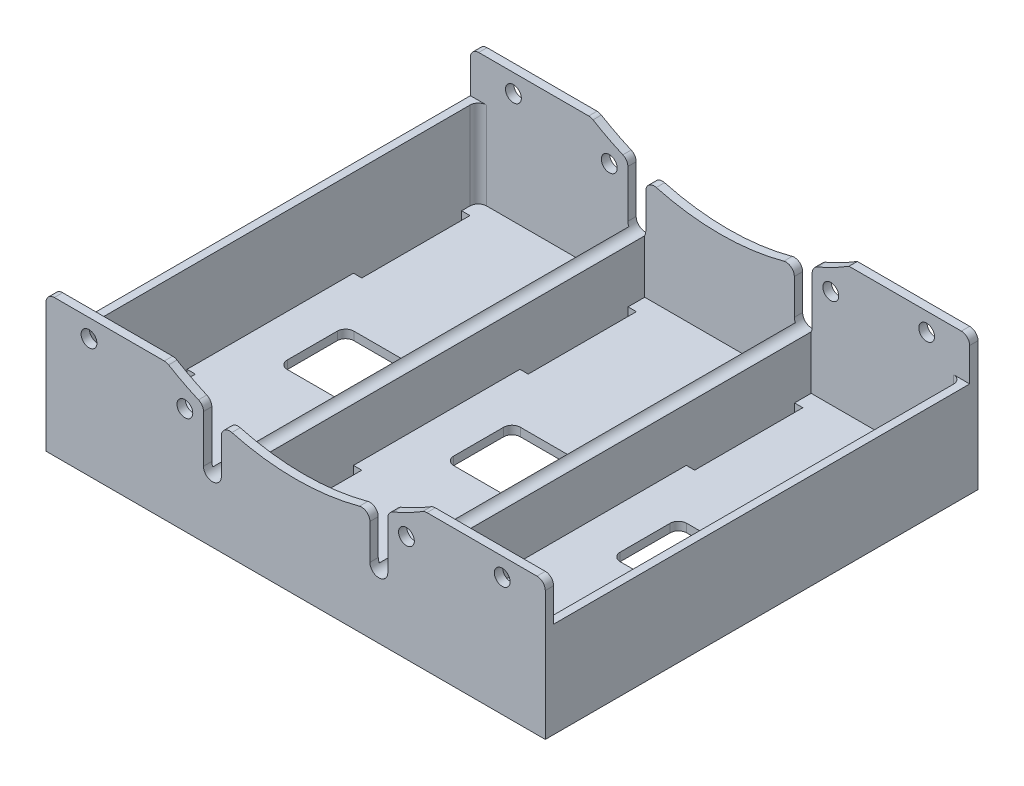
SolidWorks part; units mm, degrees
ref_plane "Front Plane" through (0, 0, 0) normal (0, 0, 1) x (1, 0, 0)
ref_plane "Top Plane" through (0, 0, 0) normal (0, 1, 0) x (1, 0, 0)
ref_plane "Right Plane" through (0, 0, 0) normal (1, 0, 0) x (0, 0, -1)
sketch "Sketch1" plane through (0, 0, 0) normal (0, 1, 0) x (1, 0, 0)
  line L1 (-60, -52) -> (60, -52)
  line L2 (-60, -52) -> (-60, 52)
  line L3 (-60, 52) -> (60, 52)
  line L4 (60, -52) -> (60, 52)
  line L5 (-60, -52) -> (60, 52) construction
  line L6 (-60, 52) -> (60, -52) construction
  point P0 (0, 0)
  dimension "D1" = 120
  dimension "D2" = 104
extrude "Boss-Extrude1" add sketch "Sketch1" along normal blind 2
sketch "Sketch3" plane through (0, 2, 0) normal (0, 1, 0) x (1, 0, 0)
  line L0 (20, 52) -> (20, 68.7594) construction
  line L1 (20, 68.7594) -> (-20, 68.7594) construction
  line L2 (60, 52) -> (-60, 52) construction
  line L3 (-21.8986, 52) -> (-18.1014, 52) construction
  line L4 (-21.8986, 52) -> (-21.8986, -52) construction
  line L5 (-60, -52) -> (60, -52) construction
  line L6 (-20, 68.7594) -> (-20, 52) construction
  line L7 (-18.1014, 52) -> (-18.1014, -52) construction
  line L8 (-18.1014, -52) -> (18.1014, 52) construction
  line L9 (18.1014, 52) -> (18.1014, -52) construction
  line L10 (18.1014, 52) -> (21.8986, 52) construction
  line L11 (21.8986, 52) -> (21.8986, -52) construction
  line L12 (0, 0) -> (0, 52) construction
  line L13 (-18.1014, 52) -> (-16.3514, 52) construction
  line L14 (-18.1014, 52) -> (-18.1014, -52) construction
  line L15 (-18.1014, -52) -> (-16.3514, -52) construction
  line L16 (-16.3514, 52) -> (-16.3514, -52) construction
  line L17 (-23.6486, 52) -> (-21.8986, 52) construction
  line L18 (-23.6486, 52) -> (-23.6486, -52) construction
  line L19 (-23.6486, -52) -> (-21.8986, -52) construction
  line L20 (-21.8986, 52) -> (-21.8986, -52) construction
  line L21 (21.8986, 52) -> (21.8986, -52) construction
  line L22 (23.6486, -52) -> (21.8986, -52) construction
  line L23 (23.6486, 52) -> (23.6486, -52) construction
  line L24 (23.6486, 52) -> (21.8986, 52) construction
  line L25 (16.3514, 52) -> (16.3514, -52) construction
  line L26 (18.1014, -52) -> (16.3514, -52) construction
  line L27 (18.1014, 52) -> (18.1014, -52) construction
  line L28 (18.1014, 52) -> (16.3514, 52) construction
  line L30 (-21.8986, 52) -> (-18.1014, 52)
  line L31 (-21.8986, 52) -> (-21.8986, -52)
  line L32 (-21.8986, -52) -> (-18.1014, -52)
  line L33 (-18.1014, 52) -> (-18.1014, -52)
  line L34 (18.1014, -52) -> (21.8986, -52)
  line L35 (18.1014, -52) -> (18.1014, 52)
  line L36 (18.1014, 52) -> (21.8986, 52)
  line L37 (21.8986, -52) -> (21.8986, 52)
  dimension "D1" = 3.7973
  dimension "D2" = 40
  dimension "D3" = 1.75
extrude "Boss-Extrude3" add sketch "Sketch3" along normal blind 21
sketch "Sketch4" plane through (0, 2, 0) normal (0, 1, 0) x (1, 0, 0)
  line L1 (-60, 52) -> (-21.8986, 52)
  line L2 (-60, 52) -> (-60, 50)
  line L3 (-60, 50) -> (-21.8986, 50)
  line L4 (-21.8986, 52) -> (-21.8986, 50)
  line L6 (-18.1014, 52) -> (18.1014, 52)
  line L7 (-18.1014, 52) -> (-18.1014, 50)
  line L8 (-18.1014, 50) -> (18.1014, 50)
  line L9 (18.1014, 52) -> (18.1014, 50)
  line L10 (60, -52) -> (60, 52) construction
  line L11 (21.8986, 52) -> (60, 52)
  line L12 (21.8986, 52) -> (21.8986, 50)
  line L13 (21.8986, 50) -> (60, 50)
  line L14 (60, 52) -> (60, 50)
  line L15 (-18.1014, -52) -> (-18.1014, 52) construction
  line L16 (-21.8986, 52) -> (-21.8986, -52) construction
  line L17 (21.8986, -52) -> (21.8986, 52) construction
  line L18 (18.1014, 52) -> (18.1014, -52) construction
  line L19 (18.1014, 52) -> (-18.1014, 52) construction
  line L20 (18.1014, 52) -> (18.1014, -52) construction
  line L21 (-60, -52) -> (-21.8986, -52)
  line L22 (-60, -52) -> (-60, -50)
  line L23 (-60, -50) -> (-21.8986, -50)
  line L24 (-21.8986, -52) -> (-21.8986, -50)
  line L25 (-18.1014, -52) -> (18.1014, -52)
  line L26 (-18.1014, -52) -> (-18.1014, -50)
  line L27 (-18.1014, -50) -> (18.1014, -50)
  line L28 (18.1014, -52) -> (18.1014, -50)
  line L30 (21.8986, -52) -> (60, -52)
  line L31 (21.8986, -52) -> (21.8986, -50)
  line L32 (21.8986, -50) -> (60, -50)
  line L33 (60, -52) -> (60, -50)
  dimension "D1" = 2
extrude "Boss-Extrude4" add sketch "Sketch4" along normal up to surface (21 mm away) up to face at (-20, 23, 0)
sketch "Sketch5" plane through (0, 0, 52) normal (0, 0, 1) x (1, 0, 0)
  line L0 (-22.1487, 15.8) -> (-22.1487, 23)
  line L1 (-22.1487, 23) -> (-17.8514, 23)
  line L2 (-17.8514, 23) -> (-17.8514, 15.8)
  line L3 (-60, 23) -> (60, 23) construction
  line L4 (17.8514, 15.8) -> (17.8514, 23)
  line L6 (17.8514, 23) -> (22.1487, 23)
  line L7 (22.1487, 23) -> (22.1487, 15.8)
  line L8 (-60, 23) -> (60, 23) construction
  circle A2 centre (20, 15.8) radius 1.8986 construction
  circle A3 centre (-20, 15.8) radius 1.8986 construction
  arc A6 (-22.1487, 15.8) -> (-17.8514, 15.8) centre (-20, 15.8) ccw
  arc A7 (17.8514, 15.8) -> (22.1487, 15.8) centre (20, 15.8) ccw
  circle A9 centre (-20, 15.8) radius 2.1486 construction
  circle A10 centre (20, 15.8) radius 2.1486 construction
  point P14 (-17.9452, 16.4282)
  point P17 (17.3979, 22)
  point P18 (22.0548, 16.4282)
  dimension "D1" = 0.25
extrude "Cut-Extrude1" cut sketch "Sketch5" against normal through all both and the other way through all
sketch "Sketch6" plane through (0, 2, 0) normal (0, 1, 0) x (1, 0, 0)
  line L0 (-60, 50) -> (-21.8986, 50) construction
  line L1 (-60, -52) -> (-58.1, -52)
  line L2 (-60, -52) -> (-60, 50)
  line L3 (-60, 50) -> (-58.1, 50)
  line L4 (-58.1, -52) -> (-58.1, 50)
  line L5 (21.8986, 50) -> (60, 50) construction
  line L6 (60, -52) -> (58.1, -52)
  line L7 (60, -52) -> (60, 50)
  line L8 (60, 50) -> (58.1, 50)
  line L9 (58.1, -52) -> (58.1, 50)
  point P14 (60, -52)
  point P16 (-60, -52)
  dimension "D1" = 1.9
extrude "Boss-Extrude5" add sketch "Sketch6" along normal up to surface (21 mm away) up to face at (-41.0743, 23, -51)
sketch "Sketch7" plane through (0, 2, 0) normal (0, 1, 0) x (1, 0, 0)
  line L0 (0, 0) -> (-58.1, 0) construction
  line L1 (-58.1, -50) -> (-58.1, 50) construction
  line L2 (-18.1014, -50) -> (-18.1014, 50) construction
  line L3 (-58.1, 46) -> (-56.1, 46)
  line L4 (-58.1, 46) -> (-58.1, 20)
  line L5 (-58.1, 20) -> (-56.1, 20)
  line L6 (-56.1, 46) -> (-56.1, 20)
  line L7 (-18.1014, 46) -> (-16.1013, 46)
  line L8 (-18.1014, 46) -> (-18.1014, 20)
  line L9 (-18.1014, 20) -> (-16.1013, 20)
  line L10 (-16.1013, 46) -> (-16.1013, 20)
  line L11 (21.8986, -50) -> (21.8986, 50) construction
  line L12 (21.8986, 46) -> (23.8987, 46)
  line L13 (21.8986, 46) -> (21.8987, 20)
  line L14 (21.8987, 20) -> (23.8987, 20)
  line L15 (23.8987, 46) -> (23.8987, 20)
  line L16 (-21.8986, 50) -> (-21.8986, -50) construction
  line L17 (-21.8986, 46) -> (-23.8987, 46)
  line L18 (-21.8986, 46) -> (-21.8986, 20)
  line L19 (-21.8986, 20) -> (-23.8986, 20)
  line L20 (-23.8987, 46) -> (-23.8986, 20)
  line L21 (18.1014, -50) -> (18.1014, 50) construction
  line L22 (18.1014, 46) -> (16.1013, 46)
  line L23 (18.1014, 46) -> (18.1014, 20)
  line L24 (18.1014, 20) -> (16.1014, 20)
  line L25 (16.1013, 46) -> (16.1014, 20)
  line L26 (58.1, 50) -> (58.1, -50) construction
  line L31 (58.1, 46) -> (56.1, 46)
  line L32 (58.1, 46) -> (58.1, 20)
  line L33 (58.1, 20) -> (56.1, 20)
  line L34 (56.1, 46) -> (56.1, 20)
  line L35 (56.1, -46) -> (56.1, -20)
  line L36 (58.1, -20) -> (56.1, -20)
  line L37 (58.1, -46) -> (58.1, -20)
  line L38 (58.1, -46) -> (56.1, -46)
  line L39 (16.1014, -46) -> (16.1014, -20)
  line L40 (18.1014, -20) -> (16.1014, -20)
  line L41 (18.1014, -46) -> (18.1014, -20)
  line L42 (18.1014, -46) -> (16.1014, -46)
  line L43 (-23.8986, -46) -> (-23.8986, -20)
  line L44 (-21.8986, -20) -> (-23.8986, -20)
  line L45 (-21.8986, -46) -> (-21.8986, -20)
  line L46 (-21.8986, -46) -> (-23.8986, -46)
  line L47 (23.8987, -46) -> (23.8987, -20)
  line L48 (21.8987, -20) -> (23.8987, -20)
  line L49 (21.8987, -46) -> (21.8987, -20)
  line L50 (21.8987, -46) -> (23.8987, -46)
  line L51 (-16.1013, -46) -> (-16.1013, -20)
  line L52 (-18.1013, -20) -> (-16.1013, -20)
  line L53 (-18.1013, -46) -> (-18.1013, -20)
  line L54 (-18.1013, -46) -> (-16.1013, -46)
  line L55 (-56.1, -46) -> (-56.1, -20)
  line L56 (-58.1, -20) -> (-56.1, -20)
  line L57 (-58.1, -46) -> (-58.1, -20)
  line L58 (-58.1, -46) -> (-56.1, -46)
  dimension "D1" = 2
  dimension "D2" = 20
  dimension "D3" = 26
extrude "Cut-Extrude2" cut sketch "Sketch7" against normal through all both
sketch "Sketch8" plane through (0, 2, 0) normal (0, 1, 0) x (1, 0, 0)
  line L0 (-21.8986, 0) -> (-58.1, 0) construction
  line L3 (-21.8986, 20) -> (-21.8986, -20) construction
  line L7 (21.8986, 0) -> (58.1, 0) construction
  line L8 (21.8986, 50) -> (21.8986, -50) construction
  line L9 (58.1, 50) -> (58.1, -50) construction
  line L11 (-58.1, -20) -> (-58.1, 20) construction
  line L12 (-47.9993, -8) -> (-31.9993, -8)
  line L13 (-47.9993, -8) -> (-47.9993, 8)
  line L14 (-47.9993, 8) -> (-31.9993, 8)
  line L15 (-31.9993, -8) -> (-31.9993, 8)
  line L16 (-47.9993, -8) -> (-31.9993, 8) construction
  line L17 (-47.9993, 8) -> (-31.9993, -8) construction
  line L18 (-8, -8) -> (8, -8)
  line L19 (-8, -8) -> (-8, 8)
  line L20 (-8, 8) -> (8, 8)
  line L21 (8, -8) -> (8, 8)
  line L22 (-8, -8) -> (8, 8) construction
  line L23 (-8, 8) -> (8, -8) construction
  line L24 (31.9993, -8) -> (47.9993, -8)
  line L25 (31.9993, -8) -> (31.9993, 8)
  line L26 (31.9993, 8) -> (47.9993, 8)
  line L27 (47.9993, -8) -> (47.9993, 8)
  line L28 (31.9993, -8) -> (47.9993, 8) construction
  line L29 (31.9993, 8) -> (47.9993, -8) construction
  point P6 (-39.9993, 0)
  point P7 (-39.9993, 0)
  point P23 (0, 0)
  point P29 (39.9993, 0)
  dimension "D1" = 16
extrude "Cut-Extrude3" cut sketch "Sketch8" against normal through all both
fillet "Fillet1" radius 2 12 edges at (47.9993, 1, 8) (31.9993, 1, 8) (31.9993, 1, -8) (47.9993, 1, -8) (8, 1, -8) (-8, 1, -8) (-8, 1, 8) (8, 1, 8) (-31.9993, 1, 8) (-47.9993, 1, 8) (-31.9993, 1, -8) (-47.9993, 1, -8)
sketch "Sketch9" plane through (0, 0, -50) normal (0, 0, 1) x (1, 0, 0)
  line L1 (0, 24.2) -> (0, 44.7462) construction
  line L2 (-30.9994, 33) -> (-60, 33)
  line L4 (-60, 23) -> (-60, 0) construction
  line L5 (-60, 33) -> (-60, 23)
  line L6 (-60, 23) -> (60, 23)
  line L7 (-17.8514, 23) -> (17.8514, 23) construction
  line L8 (0, 23) -> (0, 24.2) construction
  line L9 (60, 33) -> (60, 23)
  line L10 (30.9994, 33) -> (60, 33)
  line L11 (-60, 23) -> (-60, 0) construction
  arc A4 (30.9994, 33) -> (-30.9994, 33) centre (0, 83.2) cw
  circle A6 centre (-49.6579, 28.5871) radius 1.8987
  circle A8 centre (49.6579, 28.5871) radius 1.8987
  circle A10 centre (26.625, 25.5492) radius 1.8987
  circle A12 centre (-26.625, 25.5492) radius 1.8987
  point P19 (-60, 0)
  point P22 (0, 15.5215)
  point P25 (0, 44.7462)
  dimension "D1" = 10
extrude "Boss-Extrude6" add sketch "Sketch9" against normal up to surface (2 mm away) up to face at (0, 16.4086, -52)
sketch "Sketch10" plane through (0, 0, 52) normal (0, 0, 1) x (1, 0, 0)
  line L0 (60, 23) -> (60, 33) construction
  line L1 (60, 33) -> (30.9994, 33) construction
  line L2 (-30.9994, 33) -> (-60, 33) construction
  line L3 (-60, 33) -> (-60, 23) construction
  line L4 (60, 23) -> (60, 33)
  line L5 (60, 33) -> (30.9994, 33)
  line L6 (-30.9994, 33) -> (-60, 33)
  line L7 (-60, 33) -> (-60, 23)
  line L8 (-60, 23) -> (60, 23)
  circle A0 centre (49.6579, 28.5871) radius 1.8987 construction
  circle A1 centre (26.625, 25.5492) radius 1.8987 construction
  circle A2 centre (-26.625, 25.5492) radius 1.8987 construction
  circle A3 centre (-49.6579, 28.5871) radius 1.8987 construction
  arc A4 (-30.9994, 33) -> (30.9994, 33) centre (0, 83.2) ccw construction
  circle A5 centre (49.6579, 28.5871) radius 1.8987
  circle A6 centre (26.625, 25.5492) radius 1.8987
  circle A7 centre (-26.625, 25.5492) radius 1.8987
  circle A8 centre (-49.6579, 28.5871) radius 1.8987
  arc A9 (-30.9994, 33) -> (30.9994, 33) centre (0, 83.2) ccw
extrude "Boss-Extrude7" add sketch "Sketch10" against normal up to surface (2 mm away) up to face at (-34.0594, 13.4298, 50)
sketch "Sketch11" plane through (0, 0, 52) normal (0, 0, 1) x (1, 0, 0)
  line L0 (-17.8514, 23) -> (-17.8514, 15.8) construction
  line L1 (-22.1487, 23) -> (-17.8514, 23)
  line L2 (-22.1487, 23) -> (-22.1487, 43)
  line L3 (-22.1487, 43) -> (-17.8514, 43)
  line L4 (-17.8514, 23) -> (-17.8514, 43)
  line L6 (22.1487, 23) -> (17.8514, 23)
  line L7 (22.1487, 23) -> (22.1487, 43)
  line L8 (22.1487, 43) -> (17.8514, 43)
  line L9 (17.8514, 23) -> (17.8514, 43)
  point P5 (17.8514, 23)
  dimension "D1" = 20
extrude "Cut-Extrude4" cut sketch "Sketch11" against normal through all both
fillet "Fillet2" radius 2 4 edges at (58.1, 12.5, 50) (-58.1, 12.5, 50) (58.1, 12.5, -50) (-58.1, 12.5, -50)
fillet "Fillet3" radius 2 15 edges at (60, 33, 51) (30.9994, 33, 51) (-30.9994, 33, -51) (-30.9994, 33, 51) (22.1487, 28.5151, 51) (17.8514, 26.9654, 51) (-17.8514, 26.9654, 51) (-22.1487, 28.5151, 51) (-60, 33, 51) (-60, 33, -51) (60, 33, -51) (22.1487, 28.5151, -51) (17.8514, 26.9654, -51) (-22.1487, 28.5151, -51) (-17.8514, 26.9654, -51)
